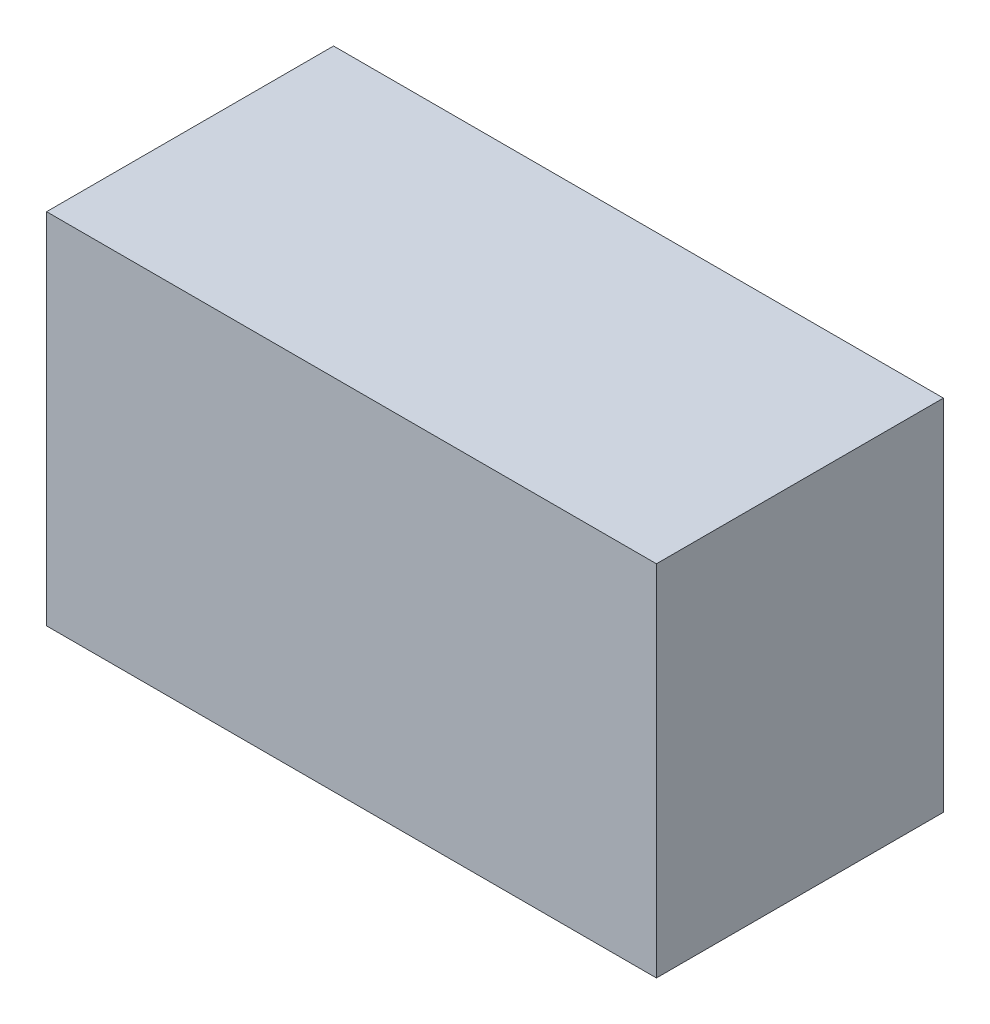
SolidWorks part; units mm, degrees
ref_plane "Front Plane" through (0, 0, 0) normal (0, 0, 1) x (1, 0, 0)
ref_plane "Top Plane" through (0, 0, 0) normal (0, 1, 0) x (1, 0, 0)
ref_plane "Right Plane" through (0, 0, 0) normal (1, 0, 0) x (0, 0, -1)
sketch "Sketch1" plane through (0, 0, 0) normal (0, 0, 1) x (1, 0, 0)
  line L1 (-107.95, 63.5) -> (107.95, 63.5)
  line L2 (-107.95, 63.5) -> (-107.95, -63.5)
  line L3 (-107.95, -63.5) -> (107.95, -63.5)
  line L4 (107.95, 63.5) -> (107.95, -63.5)
  line L5 (-107.95, 63.5) -> (107.95, -63.5) construction
  line L6 (-107.95, -63.5) -> (107.95, 63.5) construction
  point P0 (0, 0)
  dimension "D1" = 127
  dimension "D2" = 215.9
extrude "Boss-Extrude1" add sketch "Sketch1" along normal blind 101.6
sketch "Sketch2" plane through (0, 63.5, 0) normal (0, 1, 0) x (1, 0, 0)
  text T0 "ELECTRONICS" font "Century Gothic" height 25.4
